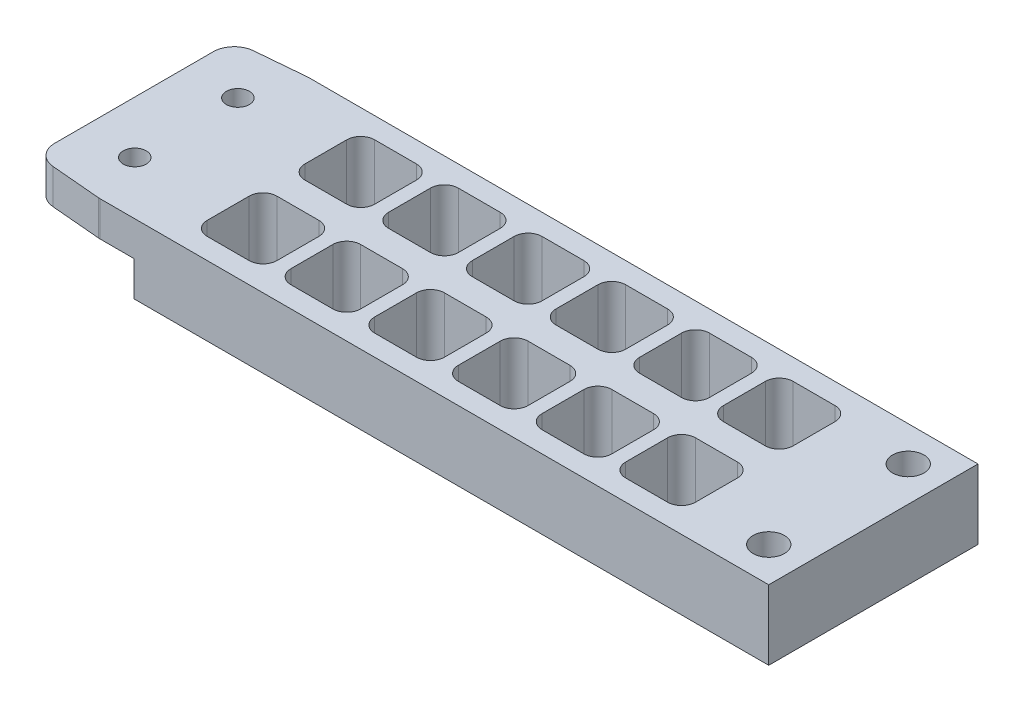
SolidWorks part; units mm, degrees
material "3.1355 (EN-AW 2024)"
ref_plane "Front" through (0, 0, 0) normal (0, 0, 1) x (1, 0, 0)
ref_plane "Top" through (0, 0, 0) normal (0, 1, 0) x (1, 0, 0)
ref_plane "Right" through (0, 0, 0) normal (1, 0, 0) x (0, 0, -1)
sketch "Эскиз1" plane through (0, 0, 0) normal (0, 1, 0) x (1, 0, 0)
  line L0 (106, 15) -> (15, 15) construction
  line L1 (15, 0) -> (106, 0)
  line L2 (0, 0) -> (0, 30) construction
  line L3 (15, 30) -> (106, 30)
  line L4 (106, 0) -> (106, 30)
  line L5 (0, 0) -> (15, 0) construction
  line L6 (0, 0.8749) -> (0, 29.1251)
  line L7 (15, 30) -> (10, 30)
  line L8 (10, 30) -> (0, 29.1251)
  line L9 (10, 0) -> (0, 0.8749)
  line L10 (15, 0) -> (10, 0)
  arc A0 (15, 30) -> (15, 0) centre (15, 15) ccw construction
  point P13 (0, 15)
  dimension "D1" = 30
  dimension "D2" = 106
  dimension "D4" = 5
  dimension "D5" = 85
extrude "Бобышка-Вытянуть1" add sketch "Эскиз1" along normal blind 10
sketch "Эскиз4" plane through (0, 0, 0) normal (0, -1, 0) x (1, 0, 0)
  line L0 (10, 0) -> (106, 0) construction
  line L1 (0, -30) -> (15, -30)
  line L2 (0, -30) -> (0, 0)
  line L3 (0, 0) -> (15, 0)
  line L4 (15, -30) -> (15, 0)
  line L5 (0, -29.1251) -> (0, -0.8749) construction
  line L6 (106, -30) -> (10, -30) construction
  dimension "D1" = 15
extrude "Вырез-Вытянуть2" cut sketch "Эскиз4" against normal blind 5
fillet "Скругление1" radius 3 4 edges at (10, 7.5, -30) (0, 7.5, -29.1251) (0, 7.5, -0.8749) (10, 7.5, 0)
sketch "Эскиз5" plane through (0, 0, 0) normal (0, -1, 0) x (1, 0, 0)
  line L0 (106, -15) -> (96, -15) construction
  line L1 (106, 0) -> (106, -30) construction
  line L2 (15, -15) -> (20.5, -15) construction
  line L3 (15, -30) -> (15, 0) construction
  line L4 (106, -30) -> (15, -30) construction
  line L5 (22.5, -17) -> (28.5, -17)
  line L6 (20.5, -19) -> (20.5, -25)
  line L7 (22.5, -27) -> (28.5, -27)
  line L8 (30.5, -19) -> (30.5, -25)
  line L9 (20.5, -17) -> (30.5, -27) construction
  line L10 (20.5, -27) -> (30.5, -17) construction
  line L11 (34.5, -17) -> (40.5, -17)
  line L12 (32.5, -19) -> (32.5, -25)
  line L13 (34.5, -27) -> (40.5, -27)
  line L14 (42.5, -19) -> (42.5, -25)
  line L15 (32.5, -17) -> (42.5, -27) construction
  line L16 (32.5, -27) -> (42.5, -17) construction
  line L17 (46.5, -17) -> (52.5, -17)
  line L18 (44.5, -19) -> (44.5, -25)
  line L19 (46.5, -27) -> (52.5, -27)
  line L20 (54.5, -19) -> (54.5, -25)
  line L21 (44.5, -17) -> (54.5, -27) construction
  line L22 (44.5, -27) -> (54.5, -17) construction
  line L23 (58.5, -17) -> (64.5, -17)
  line L24 (56.5, -19) -> (56.5, -25)
  line L25 (58.5, -27) -> (64.5, -27)
  line L26 (66.5, -19) -> (66.5, -25)
  line L27 (56.5, -17) -> (66.5, -27) construction
  line L28 (56.5, -27) -> (66.5, -17) construction
  line L29 (70.5, -17) -> (76.5, -17)
  line L30 (68.5, -19) -> (68.5, -25)
  line L31 (70.5, -27) -> (76.5, -27)
  line L32 (78.5, -19) -> (78.5, -25)
  line L33 (68.5, -17) -> (78.5, -27) construction
  line L34 (68.5, -27) -> (78.5, -17) construction
  line L35 (82.5, -17) -> (88.5, -17)
  line L36 (80.5, -19) -> (80.5, -25)
  line L37 (82.5, -27) -> (88.5, -27)
  line L38 (90.5, -19) -> (90.5, -25)
  line L39 (80.5, -17) -> (90.5, -27) construction
  line L40 (80.5, -27) -> (90.5, -17) construction
  line L41 (25.5, -22) -> (37.5, -22) construction
  line L42 (25.5, -8) -> (37.5, -8) construction
  line L43 (80.5, -3) -> (90.5, -13) construction
  line L44 (80.5, -13) -> (90.5, -3) construction
  line L45 (68.5, -3) -> (78.5, -13) construction
  line L46 (68.5, -13) -> (78.5, -3) construction
  line L47 (56.5, -3) -> (66.5, -13) construction
  line L48 (56.5, -13) -> (66.5, -3) construction
  line L49 (44.5, -3) -> (54.5, -13) construction
  line L50 (44.5, -13) -> (54.5, -3) construction
  line L51 (32.5, -3) -> (42.5, -13) construction
  line L52 (32.5, -13) -> (42.5, -3) construction
  line L53 (20.5, -3) -> (30.5, -13) construction
  line L54 (20.5, -13) -> (30.5, -3) construction
  line L55 (90.5, -11) -> (90.5, -5)
  line L56 (82.5, -3) -> (88.5, -3)
  line L57 (80.5, -11) -> (80.5, -5)
  line L58 (82.5, -13) -> (88.5, -13)
  line L59 (78.5, -11) -> (78.5, -5)
  line L60 (70.5, -3) -> (76.5, -3)
  line L61 (68.5, -11) -> (68.5, -5)
  line L62 (70.5, -13) -> (76.5, -13)
  line L63 (66.5, -11) -> (66.5, -5)
  line L64 (58.5, -3) -> (64.5, -3)
  line L65 (56.5, -11) -> (56.5, -5)
  line L66 (58.5, -13) -> (64.5, -13)
  line L67 (54.5, -11) -> (54.5, -5)
  line L68 (46.5, -3) -> (52.5, -3)
  line L69 (44.5, -11) -> (44.5, -5)
  line L70 (46.5, -13) -> (52.5, -13)
  line L71 (42.5, -11) -> (42.5, -5)
  line L72 (34.5, -3) -> (40.5, -3)
  line L73 (32.5, -11) -> (32.5, -5)
  line L74 (34.5, -13) -> (40.5, -13)
  line L75 (30.5, -11) -> (30.5, -5)
  line L76 (22.5, -3) -> (28.5, -3)
  line L77 (20.5, -11) -> (20.5, -5)
  line L78 (22.5, -13) -> (28.5, -13)
  arc A0 (28.5, -27) -> (30.5, -25) centre (28.5, -25) ccw
  arc A1 (22.5, -27) -> (20.5, -25) centre (22.5, -25) cw
  arc A2 (20.5, -19) -> (22.5, -17) centre (22.5, -19) cw
  arc A3 (28.5, -17) -> (30.5, -19) centre (28.5, -19) cw
  arc A4 (40.5, -27) -> (42.5, -25) centre (40.5, -25) ccw
  arc A5 (34.5, -27) -> (32.5, -25) centre (34.5, -25) cw
  arc A6 (32.5, -19) -> (34.5, -17) centre (34.5, -19) cw
  arc A7 (40.5, -17) -> (42.5, -19) centre (40.5, -19) cw
  arc A8 (52.5, -27) -> (54.5, -25) centre (52.5, -25) ccw
  arc A9 (46.5, -27) -> (44.5, -25) centre (46.5, -25) cw
  arc A10 (44.5, -19) -> (46.5, -17) centre (46.5, -19) cw
  arc A11 (52.5, -17) -> (54.5, -19) centre (52.5, -19) cw
  arc A12 (64.5, -27) -> (66.5, -25) centre (64.5, -25) ccw
  arc A13 (58.5, -27) -> (56.5, -25) centre (58.5, -25) cw
  arc A14 (56.5, -19) -> (58.5, -17) centre (58.5, -19) cw
  arc A15 (64.5, -17) -> (66.5, -19) centre (64.5, -19) cw
  arc A16 (76.5, -27) -> (78.5, -25) centre (76.5, -25) ccw
  arc A17 (70.5, -27) -> (68.5, -25) centre (70.5, -25) cw
  arc A18 (68.5, -19) -> (70.5, -17) centre (70.5, -19) cw
  arc A19 (76.5, -17) -> (78.5, -19) centre (76.5, -19) cw
  arc A20 (88.5, -27) -> (90.5, -25) centre (88.5, -25) ccw
  arc A21 (82.5, -27) -> (80.5, -25) centre (82.5, -25) cw
  arc A22 (80.5, -19) -> (82.5, -17) centre (82.5, -19) cw
  arc A23 (88.5, -17) -> (90.5, -19) centre (88.5, -19) cw
  arc A24 (88.5, -13) -> (90.5, -11) centre (88.5, -11) ccw
  arc A25 (80.5, -11) -> (82.5, -13) centre (82.5, -11) ccw
  arc A26 (82.5, -3) -> (80.5, -5) centre (82.5, -5) ccw
  arc A27 (88.5, -3) -> (90.5, -5) centre (88.5, -5) cw
  arc A28 (76.5, -13) -> (78.5, -11) centre (76.5, -11) ccw
  arc A29 (68.5, -11) -> (70.5, -13) centre (70.5, -11) ccw
  arc A30 (70.5, -3) -> (68.5, -5) centre (70.5, -5) ccw
  arc A31 (76.5, -3) -> (78.5, -5) centre (76.5, -5) cw
  arc A32 (64.5, -13) -> (66.5, -11) centre (64.5, -11) ccw
  arc A33 (56.5, -11) -> (58.5, -13) centre (58.5, -11) ccw
  arc A34 (58.5, -3) -> (56.5, -5) centre (58.5, -5) ccw
  arc A35 (64.5, -3) -> (66.5, -5) centre (64.5, -5) cw
  arc A36 (52.5, -13) -> (54.5, -11) centre (52.5, -11) ccw
  arc A37 (44.5, -11) -> (46.5, -13) centre (46.5, -11) ccw
  arc A38 (46.5, -3) -> (44.5, -5) centre (46.5, -5) ccw
  arc A39 (52.5, -3) -> (54.5, -5) centre (52.5, -5) cw
  arc A40 (40.5, -13) -> (42.5, -11) centre (40.5, -11) ccw
  arc A41 (32.5, -11) -> (34.5, -13) centre (34.5, -11) ccw
  arc A42 (34.5, -3) -> (32.5, -5) centre (34.5, -5) ccw
  arc A43 (40.5, -3) -> (42.5, -5) centre (40.5, -5) cw
  arc A44 (28.5, -13) -> (30.5, -11) centre (28.5, -11) ccw
  arc A45 (20.5, -11) -> (22.5, -13) centre (22.5, -11) ccw
  arc A46 (22.5, -3) -> (20.5, -5) centre (22.5, -5) ccw
  arc A47 (28.5, -3) -> (30.5, -5) centre (28.5, -5) cw
  point P8 (25.5, -22)
  point P28 (37.5, -22)
  point P45 (49.5, -22)
  point P62 (61.5, -22)
  point P79 (73.5, -22)
  point P96 (85.5, -22)
  point P212 (85.5, -8)
  point P213 (73.5, -8)
  point P214 (61.5, -8)
  point P215 (49.5, -8)
  dimension "D5" = 2
  dimension "D1" = 10
  dimension "D2" = 5.5
  dimension "D3" = 10
  dimension "D4" = 3
  dimension "D7" = 12
  dimension "D6" = 6
extrude "Вырез-Вытянуть3" cut sketch "Эскиз5" against normal through all
sketch "Эскиз6" plane through (0, 10, 0) normal (0, 1, 0) x (1, 0, 0)
  line L0 (101, 30) -> (101, 0) construction
  line L1 (106, 30) -> (10.131, 30) construction
  line L2 (10.131, 0) -> (106, 0) construction
  line L3 (106, 0) -> (106, 30) construction
  point P8 (101, 25)
  point P9 (101, 5)
  dimension "D1" = 5
  dimension "D2" = 5
  dimension "D3" = 5
hole_wizard "Отверстие с зазором M41" positions "Эскиз8" profile "Эскиз7" hole size "M4" standard "Ansi Metric" end condition through all
sketch "Эскиз8" plane through (0, 10, 0) normal (0, 1, 0) x (1, 0, 0)
  point P0 (101, 25)
  point P3 (101, 5)
sketch "Эскиз7" plane through (101, 10, -25) normal (1, 0, 0) x (0, 0, 1)
  line L0 (0, 0) -> (0, 10)
  line L1 (0, 10) -> (2.25, 10)
  line L2 (2.25, 10) -> (2.25, 0)
  line L5 (2.25, 0) -> (0, 0)
  line L11 (0, -6.35) -> (0, 107.95) construction
  dimension "Диаметр сквозного отверстия" = 4.5
  dimension "Глубина сквозного отверстия" = 10
sketch "Эскиз10" plane through (0, 5, 0) normal (0, -1, 0) x (1, 0, 0)
  line L0 (0, -15) -> (7.5, -15) construction
  line L1 (0, -3.6239) -> (0, -26.3761) construction
  line L2 (7.5, -15) -> (7.5, -29.7813) construction
  line L3 (9.8695, -29.9886) -> (2.7385, -29.3647) construction
  line L4 (7.5, -15) -> (7.5, -0.2187) construction
  line L5 (2.7385, -0.6353) -> (9.8695, -0.0114) construction
  point P4 (7.5, -22.3906)
  point P11 (7.5, -7.6094)
  dimension "D1" = 7.5
hole_wizard "Отверстие обработанное метчиком M4x0.71" [suppressed] positions "Эскиз12" profile "Эскиз11" tap size "M4x0.7" standard "Ansi Metric"
sketch "Эскиз12" plane through (0, 5, 0) normal (0, -1, 0) x (-1, 0, 0)
  point P0 (-7.5, 15)
sketch "Эскиз11" plane through (7.5, 5, -15) normal (1, 0, 0) x (0, 0, -1)
  line L0 (0, 0) -> (0, 5)
  line L1 (0, 5) -> (1.65, 5)
  line L2 (1.65, 5) -> (1.65, 0)
  line L5 (1.65, 0) -> (0, 0)
  line L11 (0, -6.35) -> (0, 107.95) construction
  dimension "Диаметр проходного сверла" = 3.3
  dimension "Глубина проходного сверла" = 5
cosmetic thread "Отверстие резьбы1" [suppressed] parameters "D2"=4
hole_wizard "Отверстие обработанное метчиком M4x0.72" positions "Эскиз14" profile "Эскиз13" tap size "M4x0.7" standard "Ansi Metric" end condition through all
sketch "Эскиз14" plane through (0, 10, 0) normal (0, 1, 0) x (1, 0, 0)
  point P0 (7.5, 22.3906)
  point P3 (7.5, 7.6094)
sketch "Эскиз13" plane through (7.5, 10, -22.3906) normal (1, 0, 0) x (0, 0, 1)
  line L0 (0, 0) -> (0, 10)
  line L1 (0, 10) -> (1.65, 10)
  line L2 (1.65, 10) -> (1.65, 0)
  line L5 (1.65, 0) -> (0, 0)
  line L11 (0, -6.35) -> (0, 107.95) construction
  dimension "Диаметр проходного сверла" = 3.3
  dimension "Глубина проходного сверла" = 10
cosmetic thread "Отверстие резьбы2" parameters "D2"=4
cosmetic thread "Отверстие резьбы3" parameters "D2"=4
